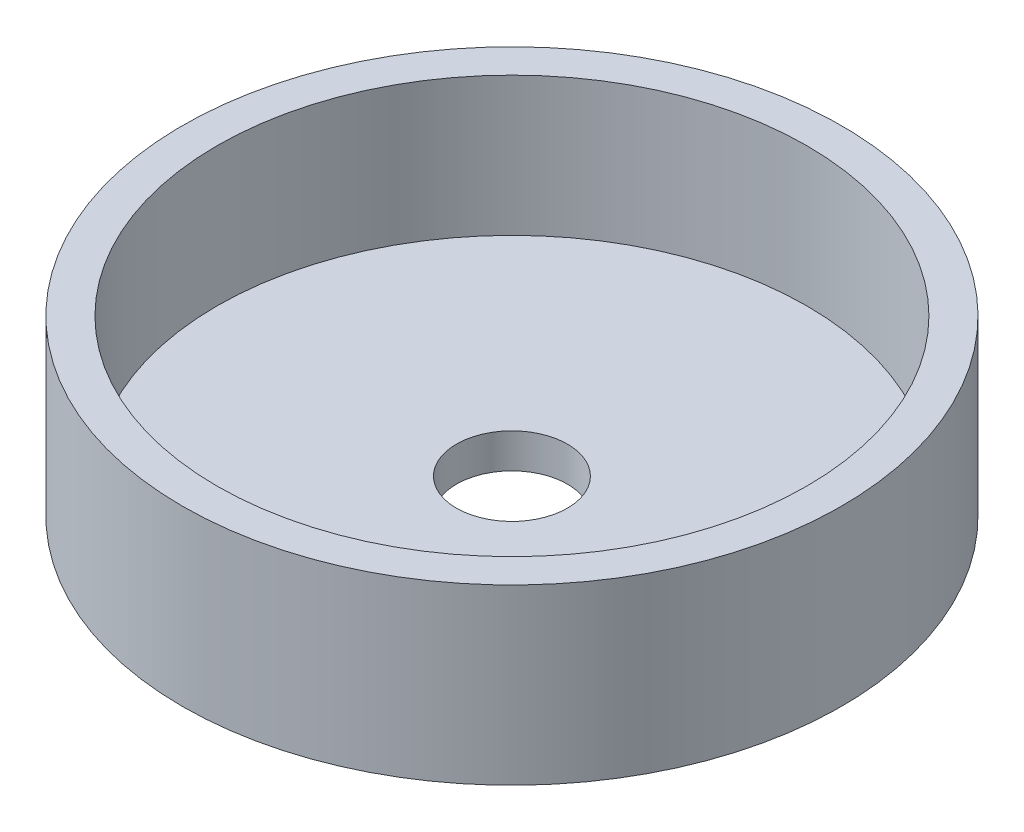
SolidWorks part; units mm, degrees
ref_plane "Front Plane" through (0, 0, 0) normal (0, 0, 1) x (1, 0, 0)
ref_plane "Top Plane" through (0, 0, 0) normal (0, 1, 0) x (1, 0, 0)
ref_plane "Right Plane" through (0, 0, 0) normal (1, 0, 0) x (0, 0, -1)
sketch "Sketch1" plane through (0, 0, 0) normal (0, 1, 0) x (1, 0, 0)
  circle A0 centre (0, 0) radius 1.6
  circle A1 centre (0, 0) radius 8.5
  circle A2 centre (0, 0) radius 9.5
  dimension "D1" = 3.2
  dimension "D2" = 17
  dimension "D3" = 1
extrude "Boss-Extrude1" add sketch "Sketch1" along normal blind 1 contours A1 A0 | A2 A1 region at (-8.2596, 0, 0) region at (-9.2313, 0, 0)
extrude "Boss-Extrude2" add sketch "Sketch1<3>" along normal blind 5 contours A2 A1 region at (-9.2313, 0, 0)
sketch "Sketch1<3>" plane through (0, 0, 0) normal (0, 1, 0) x (1, 0, 0) same geometry as "Sketch1"
